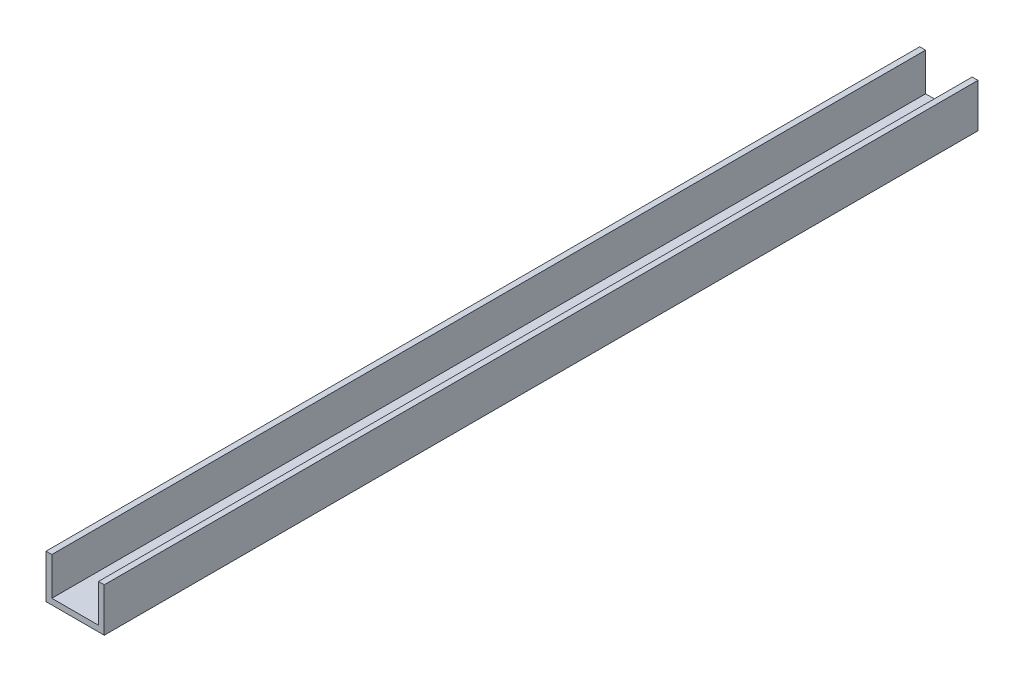
SolidWorks part; units mm, degrees
material "1060-H18 Barre (SS)"
ref_plane "Plan de face" through (0, 0, 0) normal (0, 0, 1) x (1, 0, 0)
ref_plane "Plan de dessus" through (0, 0, 0) normal (0, 1, 0) x (1, 0, 0)
ref_plane "Plan de droite" through (0, 0, 0) normal (1, 0, 0) x (0, 0, -1)
sketch "Esquisse1" plane through (0, 0, 0) normal (0, 0, 1) x (1, 0, 0)
  line L0 (-10, 0) -> (10, 0)
  line L1 (10, 0) -> (10, 15)
  line L2 (10, 15) -> (8, 15)
  line L3 (8, 15) -> (8, 2)
  line L4 (8, 2) -> (-8, 2)
  line L5 (-8, 2) -> (-8, 15)
  line L6 (-8, 15) -> (-10, 15)
  line L7 (-10, 15) -> (-10, 0)
  line L8 (0, 0) -> (0, 15.264) construction
  dimension "D1" = 2
  dimension "D2" = 2
  dimension "D3" = 15
  dimension "D4" = 20
extrude "Boss.-Extru.1" add sketch "Esquisse1" along normal blind 300
sketch "Esquisse2" plane through (0, 0, 0) normal (0, -1, 0) x (1, 0, 0)
  line L0 (0, 0) -> (0, 26.1584) construction
  line L1 (-10, 0) -> (10, 0) construction
  circle A0 centre (0, 6) radius 1.6
  circle A1 centre (0, 20) radius 1.6
  dimension "D1" = 3.2
  dimension "D2" = 3.2
  dimension "D3" = 14
  dimension "D4" = 6
extrude "Enlèv. mat.-Extru.1" cut sketch "Esquisse2" against normal through all
pattern_linear "Répétition linéaire1" count 2 spacing 115 along (0, 0, 1) of "Enlèv. mat.-Extru.1"
